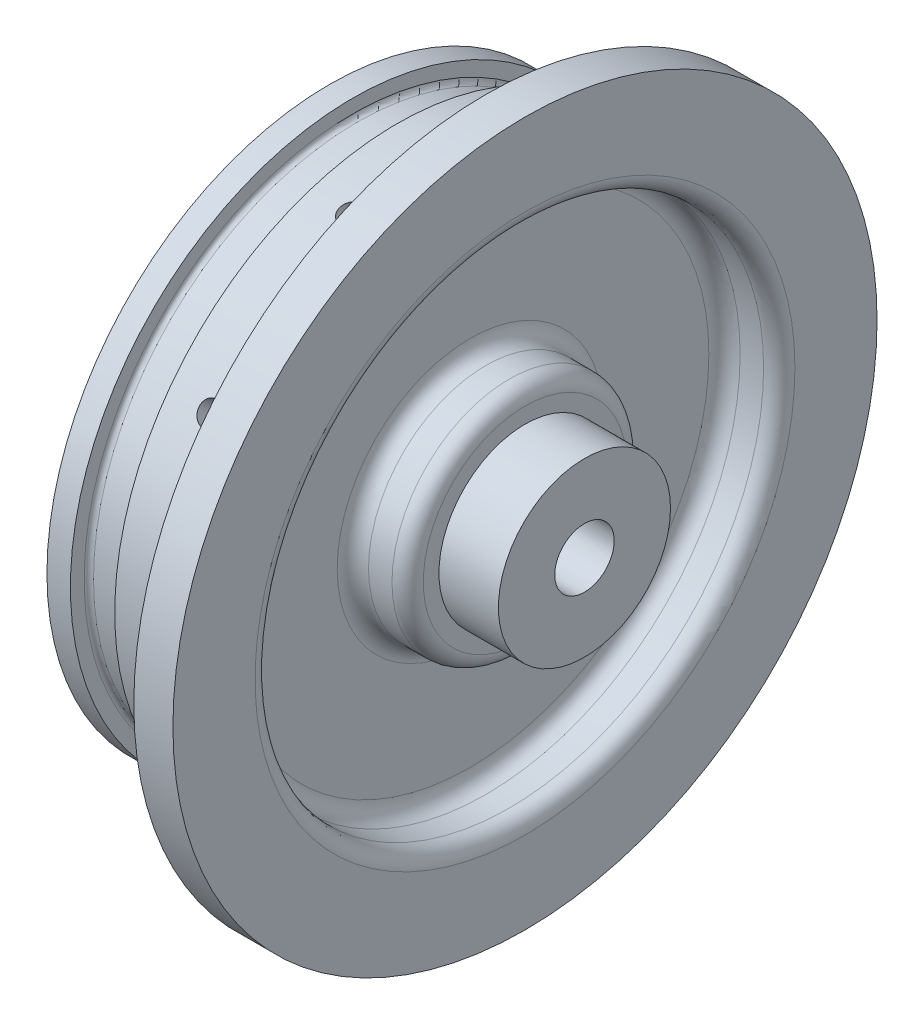
SolidWorks part; units mm, degrees
material "7075-T6 (SN)"
ref_plane "Front Plane" through (0, 0, 0) normal (0, 0, 1) x (1, 0, 0)
ref_plane "Top Plane" through (0, 0, 0) normal (0, 1, 0) x (1, 0, 0)
ref_plane "Right Plane" through (0, 0, 0) normal (1, 0, 0) x (0, 0, -1)
sketch "Sketch1" plane through (0, 0, 0) normal (1, 0, 0) x (0, 0, -1)
  circle A0 centre (0, 0) radius 57.15
  dimension "D1" = 114.3
extrude "Boss-Extrude1" add sketch "Sketch1" along normal blind 6.35
sketch "Sketch2" plane through (0, 0, 0) normal (-1, 0, 0) x (0, 0, 1)
  circle A0 centre (0, 0) radius 45.847
  dimension "D1" = 91.694
extrude "Boss-Extrude2" add sketch "Sketch2" along normal blind 25.4
sketch "Sketch10" plane through (0, 0, 0) normal (0, 1, 0) x (1, 0, 0)
  line L0 (0, 0) -> (-53.2238, 0) construction
  line L1 (-26.2636, 0) -> (26.2636, 0) construction
  line L2 (0, 0) -> (0, 64.5447) construction
  line L3 (0, -62.865) -> (0, 62.865) construction
ref_plane "Plane1" through (0, 0, -45.847) normal (0, 0, -1) x (-1, 0, 0)
sketch "Sketch11" plane through (0, 0, -45.847) normal (0, 0, -1) x (-1, 0, 0)
  line L0 (0, 0) -> (53.2238, 0) construction
  line L1 (0, -45.847) -> (0, 45.847) construction
  circle A0 centre (7.62, 0) radius 1.8986
  dimension "D2" = 3.7973
  dimension "D1" = 7.62
extrude "Cut-Extrude3" cut sketch "Sketch11" against normal blind 10.16
pattern_circular "CirPattern1" count 10 every 36 about axis through (0, 0, 0) along (-1, 0, 0) of "Cut-Extrude3" reverse direction yes
sketch "Sketch15" plane through (6.35, 0, 0) normal (1, 0, 0) x (0, 0, -1)
  circle A0 centre (0, 0) radius 4.826
  dimension "D1" = 9.652
extrude "Cut-Extrude4" cut sketch "Sketch15" against normal through all
sketch "Sketch16" plane through (0, 0, 0) normal (0, 0, 1) x (1, 0, 0)
  line L0 (0, 45.847) -> (-25.4, 45.847) construction
  line L1 (-21.59, 45.847) -> (-14.4018, 45.847)
  line L2 (-21.59, 45.847) -> (-21.59, 43.6245)
  line L3 (-20.828, 42.8625) -> (-15.1638, 42.8625)
  line L4 (-14.4018, 45.847) -> (-14.4018, 43.6245)
  line L5 (0, 0) -> (-53.2238, 0) construction
  line L6 (-25.4, 45.847) -> (-25.4, -45.847) construction
  arc A0 (-14.4018, 43.6245) -> (-15.1638, 42.8625) centre (-15.1638, 43.6245) cw
  arc A1 (-20.828, 42.8625) -> (-21.59, 43.6245) centre (-20.828, 43.6245) cw
  point P8 (-26.6119, 0)
  point P13 (-14.4018, 42.8625)
  point P16 (-21.59, 42.8625)
  dimension "D4" = 0.762
  dimension "D1" = 42.8625
  dimension "D2" = 3.81
  dimension "D3" = 7.1882
revolve "Cut-Revolve1" cut sketch "Sketch16" angle 360 about L0
sketch "Sketch17" plane through (6.35, 0, 0) normal (1, 0, 0) x (0, 0, -1)
  circle A0 centre (0, 0) radius 13.97
  circle A1 centre (0, 0) radius 4.826
  dimension "D1" = 27.94
extrude "Boss-Extrude3" add sketch "Sketch17" along normal blind 9.652
sketch "Sketch18" plane through (0, 0, 0) normal (0, 0, 1) x (1, 0, 0)
  line L0 (6.35, -57.15) -> (6.35, 57.15) construction
  line L1 (6.35, 41.275) -> (-2.54, 41.275)
  line L2 (6.35, 41.275) -> (6.35, 19.05)
  line L3 (6.35, 19.05) -> (-2.54, 19.05)
  line L4 (-2.54, 41.275) -> (-2.54, 19.05)
  line L5 (0, 0) -> (-53.2238, 0) construction
  dimension "D1" = 8.89
  dimension "D2" = 19.05
  dimension "D3" = 41.275
revolve "Cut-Revolve2" cut sketch "Sketch18" angle 360 about L0
fillet "Fillet1" radius 2.54 4 edges at (6.35, 0, -41.275) (-2.54, 0, -41.275) (-2.54, 0, -19.05) (6.35, 0, -19.05)
